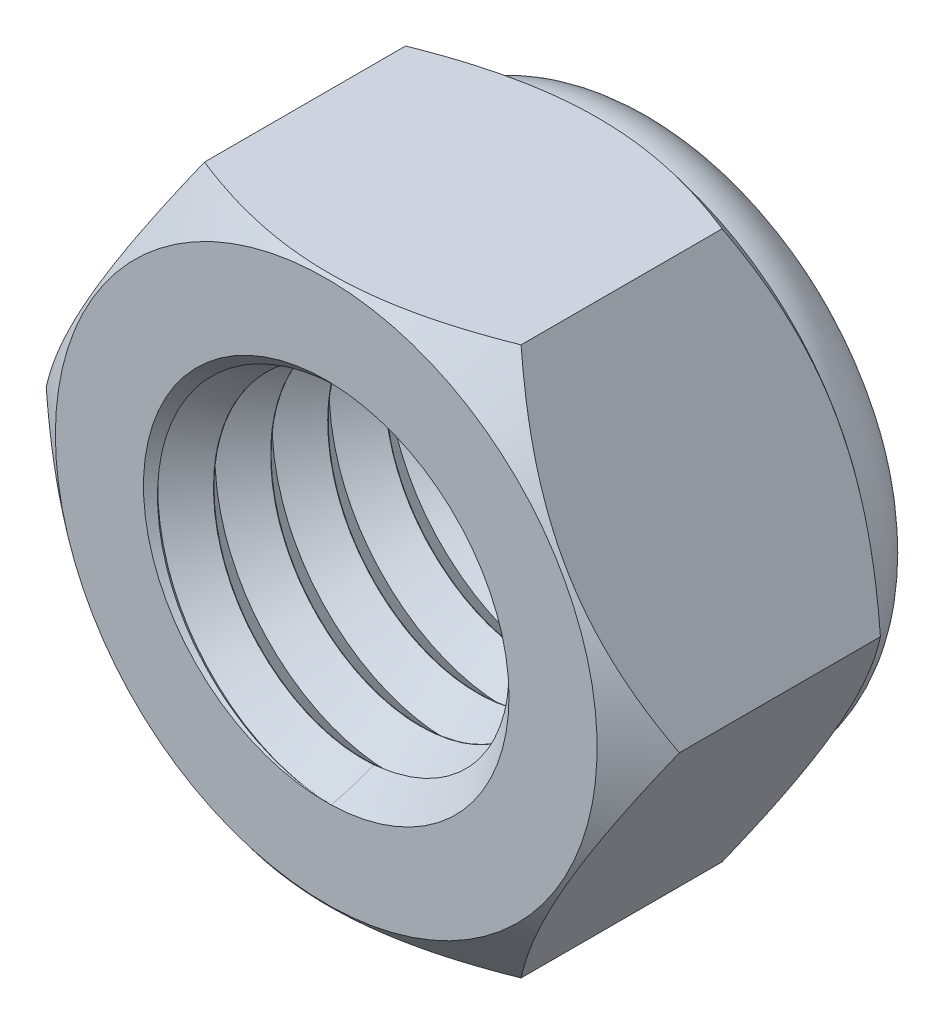
SolidWorks part; units mm, degrees
ref_plane "Plano frontal" through (0, 0, 0) normal (0, 0, 1) x (1, 0, 0)
ref_plane "Plano superior" through (0, 0, 0) normal (0, 1, 0) x (1, 0, 0)
ref_plane "Plano direito" through (0, 0, 0) normal (1, 0, 0) x (0, 0, -1)
sketch "Esboço1" plane through (0, 0, 0) normal (0, 0, 1) x (1, 0, 0)
  line L1 (6.9282, 0) -> (3.4641, 6)
  line L2 (3.4641, 6) -> (-3.4641, 6)
  line L3 (-3.4641, 6) -> (-6.9282, 0)
  line L4 (-6.9282, 0) -> (-3.4641, -6)
  line L5 (-3.4641, -6) -> (3.4641, -6)
  line L6 (3.4641, -6) -> (6.9282, 0)
  circle A0 centre (0, 0) radius 6 construction
  circle A1 centre (0, 0) radius 3.4
  dimension "D2" = 6.8
  dimension "D1" = 12
extrude "Ressalto-extrusão1" add sketch "Esboço1" along normal blind 6
sketch "Esboço2" plane through (0, 0, 0) normal (0, 1, 0) x (1, 0, 0)
  line L0 (6.9282, -6) -> (6.9282, -5.2)
  line L1 (6.9282, -6) -> (6.9282, 0) construction
  line L2 (6.9282, -5.2) -> (5.9282, -6)
  line L3 (6.9282, -6) -> (3.4641, -6) construction
  line L4 (5.9282, -6) -> (6.9282, -6)
  line L5 (6.9282, 0) -> (6.9282, -0.8)
  line L6 (6.9282, -0.8) -> (5.9282, 0)
  line L7 (6.9282, 0) -> (3.4641, 0) construction
  line L8 (5.9282, 0) -> (6.9282, 0)
  line L9 (0, 0) -> (0, -7.5375) construction
  dimension "D1" = 1
  dimension "D2" = 1
  dimension "D3" = 0.8
  dimension "D4" = 0.8
revolve "Corte-Revolução1" cut sketch "Esboço2" angle 360 about L9
chamfer "Chanfro1" distance 0.6 angle 45 1 edges at (3.4, 0, 6)
sketch "Esboço3" plane through (0, 0, 0) normal (1, 0, 0) x (0, 0, -1)
  line L0 (-8.585, 0) -> (6.2545, 0) construction
  line L1 (0, -5.9282) -> (0, 5.9282) construction
  line L2 (1.4, 4.5282) -> (1.4, 4.1282)
  line L3 (1.17, 4.5282) -> (1.17, 4.1282)
  line L4 (1.4, 4.1282) -> (1.17, 4.1282)
  line L5 (0, 5.9282) -> (0, 5.6982)
  arc A0 (0, 5.9282) -> (1.4, 4.5282) centre (0, 4.5282) cw
  arc A1 (0, 5.6982) -> (1.17, 4.5282) centre (0, 4.5282) cw
  dimension "D2" = 1.4
  dimension "D1" = 0.4
  dimension "D3" = 0.23
revolve "Revolução1" add sketch "Esboço3" angle 360 about L0
sketch "Esboço4" plane through (0, 0, 0) normal (1, 0, 0) x (0, 0, -1)
  line L0 (-10.9776, 0) -> (4.439, 0) construction
  line L2 (1.13, 4.53) -> (1.13, 3.4)
  line L3 (1.13, 3.4) -> (0.0334, 3.4)
  line L6 (0.0334, 5.6595) -> (0.0334, 3.4)
  arc A0 (0.0334, 5.6595) -> (1.13, 4.53) centre (0, 4.53) cw
  dimension "D3" = 6.8
  dimension "D4" = 1.0966
sketch "Esboço5" plane through (0, 0, 6) normal (0, 0, 1) x (1, 0, 0)
  circle A0 centre (0, 0) radius 4
  dimension "D1" = 8
curve "Hélice/Espiral1" pitch 1.25 height 8.75 radius 4 centre (0, 0, 6) axis (0, 0, -1) start towards (0, 1, 0)
sketch "Esboço6" plane through (0, 0, 0) normal (1, 0, 0) x (0, 0, -1)
  line L0 (-6, 3.4) -> (-6.62, 4)
  line L1 (-6.62, 4) -> (-7.24, 3.4)
  line L2 (-7.24, 3.4) -> (-6, 3.4)
  point P2 (-6.62, 3.4)
  point P4 (-6, 4)
  dimension "D1" = 1.24
  dimension "D2" = 0.6
sweep "Varredura de corte1" cut profiles "Esboço6" path "Hélice/Espiral1" align with end faces yes
revolve "Revolução2" add sketch "Esboço4" angle 360 about L0
